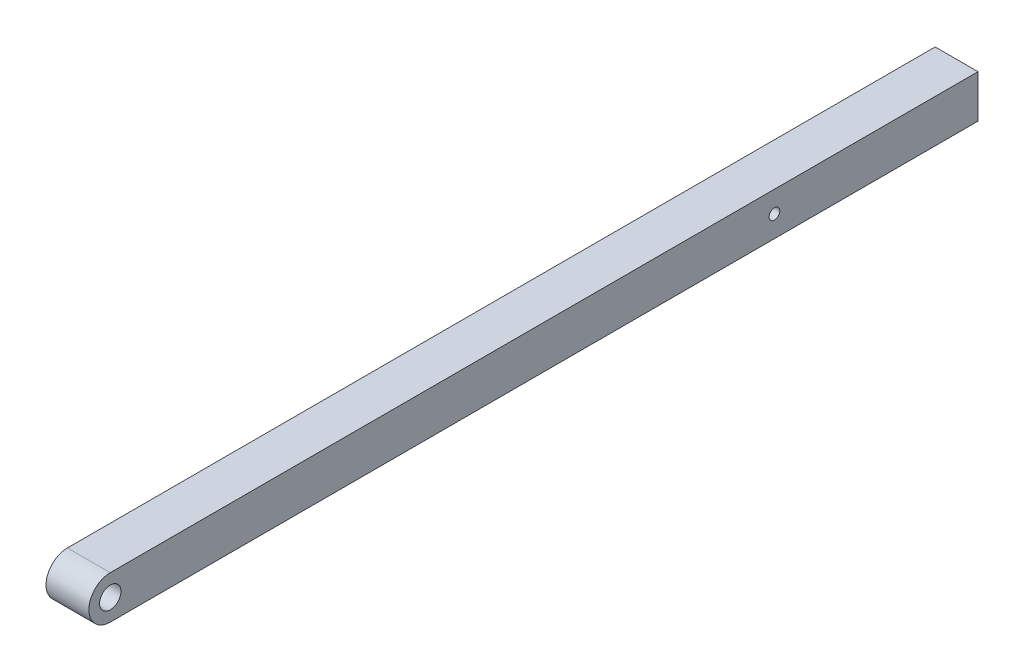
SolidWorks part; units mm, degrees
material "6061 Alloy"
ref_plane "Front Plane" through (0, 0, 0) normal (0, 0, 1) x (1, 0, 0)
ref_plane "Top Plane" through (0, 0, 0) normal (0, 1, 0) x (1, 0, 0)
ref_plane "Right Plane" through (0, 0, 0) normal (1, 0, 0) x (0, 0, -1)
sketch "Sketch1" plane through (0, 0, 0) normal (1, 0, 0) x (0, 0, -1)
  line L0 (0, 12.7) -> (514.35, 12.7)
  line L1 (0, -12.7) -> (514.35, -12.7)
  line L2 (514.35, 12.7) -> (514.35, 28.575) construction
  line L3 (514.35, 28.575) -> (520.7, 28.575) construction
  line L4 (520.7, 28.575) -> (520.7, -28.575) construction
  line L5 (520.7, -28.575) -> (514.35, -28.575) construction
  line L6 (514.35, -28.575) -> (514.35, -12.7) construction
  line L7 (514.35, 19.05) -> (558.8, 19.05) construction
  line L8 (558.8, 19.05) -> (558.8, -19.05) construction
  line L9 (558.8, -19.05) -> (514.35, -19.05) construction
  line L10 (514.35, 12.7) -> (514.35, -12.7)
  circle A0 centre (0, 0) radius 6.35
  arc A1 (0, -12.7) -> (0, 12.7) centre (0, 0) cw
  circle A4 centre (558.8, 0) radius 6.35 construction
  point P17 (520.7, 0)
  dimension "D1" = 12.7
  dimension "D2" = 12.7
  dimension "D6" = 38.1
  dimension "D3" = 6.35
  dimension "D4" = 57.15
  dimension "D7" = 558.8
  dimension "D8" = 25.4
  dimension "D9" = 38.1
extrude "Boss-Extrude1" add sketch "Sketch1" along normal blind 25.4
hole_wizard "1/4-20 Tapped Hole1" positions "Sketch3" profile "Sketch2" tap size "1/4-20" standard "ANSI Inch"
sketch "Sketch3" plane through (0, 0, -514.35) normal (0, 0, -1) x (-1, 0, 0)
  line L0 (0, 0) -> (-6.35, 0) construction
  line L2 (-6.35, 0) -> (-19.05, 0) construction
  line L3 (-19.05, 0) -> (-25.4, 0) construction
  line L5 (0, -12.7) -> (0, 12.7) construction
  line L6 (-25.4, -12.7) -> (-25.4, 12.7) construction
  point P13 (-6.35, 0)
  point P15 (-19.05, 0)
  dimension "D1" = 12.7
sketch "Sketch2" plane through (6.35, 0, -514.35) normal (1, 0, 0) x (0, 1, 0)
  line L0 (0, 0) -> (0, 18.0438)
  line L1 (0, 18.0438) -> (2.5527, 16.51)
  line L2 (2.5527, 16.51) -> (2.5527, 0)
  line L5 (2.5527, 0) -> (0, 0)
  line L10 (0, 18.0438) -> (-2.5527, 16.51) construction
  line L11 (0, -6.35) -> (0, 107.95) construction
  dimension "Tap Drill Dia." = 5.1054
  dimension "Tap Drill Depth" = 16.51
  dimension "Drill Angle" = 118
sketch "Sketch4" plane through (25.4, 0, 0) normal (1, 0, 0) x (0, 0, -1)
  line L0 (0, 0) -> (393.7, 0) construction
  circle A0 centre (393.7, 0) radius 3.175
  dimension "D1" = 6.35
  dimension "D2" = 393.7
extrude "Cut-Extrude1" cut sketch "Sketch4" against normal blind 38.1
